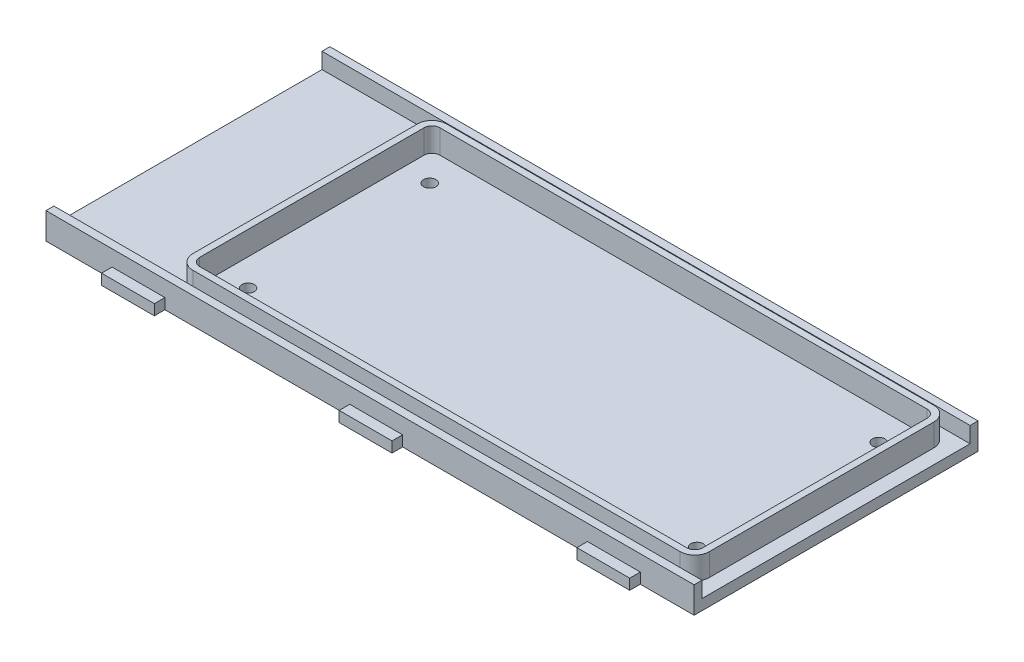
SolidWorks part; units mm, degrees
ref_plane "Front Plane" through (0, 0, 0) normal (0, 0, 1) x (1, 0, 0)
ref_plane "Top Plane" through (0, 0, 0) normal (0, 1, 0) x (1, 0, 0)
ref_plane "Right Plane" through (0, 0, 0) normal (1, 0, 0) x (0, 0, -1)
sketch "Sketch1" plane through (0, 0, 0) normal (0, 1, 0) x (1, 0, 0)
  line L0 (-61.35, 0) -> (61.35, 0) construction
  line L1 (-61.35, 26.875) -> (-48.84, 26.875)
  line L2 (-61.35, 26.875) -> (-61.35, -26.875)
  line L3 (-61.35, -26.875) -> (-48.84, -26.875)
  line L4 (61.35, 26.875) -> (61.35, -26.875)
  line L5 (-61.35, 26.875) -> (61.35, -26.875) construction
  line L6 (-61.35, -26.875) -> (61.35, 26.875) construction
  line L8 (-48.84, -26.875) -> (-48.84, -28.875)
  line L9 (-48.84, -28.875) -> (-38.84, -28.875)
  line L10 (-38.84, -26.875) -> (-38.84, -28.875)
  line L12 (-3.84, -26.875) -> (-3.84, -28.875)
  line L13 (-3.84, -28.875) -> (6.16, -28.875)
  line L14 (6.16, -26.875) -> (6.16, -28.875)
  line L16 (41.16, -26.875) -> (41.16, -28.875)
  line L17 (41.16, -28.875) -> (51.16, -28.875)
  line L18 (51.16, -26.875) -> (51.16, -28.875)
  line L19 (41.16, 28.875) -> (51.16, 28.875)
  line L20 (51.16, 26.875) -> (51.16, 28.875)
  line L22 (41.16, 26.875) -> (41.16, 28.875)
  line L23 (-3.84, 28.875) -> (6.16, 28.875)
  line L24 (6.16, 26.875) -> (6.16, 28.875)
  line L26 (-3.84, 26.875) -> (-3.84, 28.875)
  line L27 (-48.84, 28.875) -> (-38.84, 28.875)
  line L28 (-38.84, 26.875) -> (-38.84, 28.875)
  line L30 (-48.84, 26.875) -> (-48.84, 28.875)
  line L31 (-38.84, -26.875) -> (-3.84, -26.875)
  line L32 (6.16, -26.875) -> (41.16, -26.875)
  line L33 (51.16, -26.875) -> (61.35, -26.875)
  line L34 (51.16, 26.875) -> (61.35, 26.875)
  line L35 (6.16, 26.875) -> (41.16, 26.875)
  line L36 (-38.84, 26.875) -> (-3.84, 26.875)
  point P0 (0, 0)
  dimension "D1" = 53.75
  dimension "D2" = 122.7
  dimension "D3" = 10
  dimension "D4" = 10
  dimension "D5" = 10
  dimension "D6" = 2
  dimension "D7" = 2
  dimension "D8" = 2
  dimension "D9" = 12.51
  dimension "D10" = 35
  dimension "D11" = 35
extrude "Boss-Extrude1" add sketch "Sketch1" along normal blind 2
sketch "Sketch2" plane through (0, 2, 0) normal (0, 1, 0) x (1, 0, 0)
  line L0 (61.35, -26.875) -> (61.35, 26.875) construction
  line L1 (-61.35, 26.875) -> (61.35, 26.875)
  line L2 (-61.35, 26.875) -> (-61.35, 25.375)
  line L3 (-61.35, 25.375) -> (61.35, 25.375)
  line L4 (61.35, 26.875) -> (61.35, 25.375)
  line L5 (0, 0) -> (61.35, 0) construction
  line L6 (-61.35, -25.375) -> (61.35, -25.375)
  line L7 (61.35, -26.875) -> (61.35, -25.375)
  line L8 (-61.35, -26.875) -> (61.35, -26.875)
  line L9 (-61.35, -26.875) -> (-61.35, -25.375)
  dimension "D1" = 1.5
extrude "Boss-Extrude2" add sketch "Sketch2" along normal blind 3
sketch "Sketch3" plane through (0, 2, 0) normal (0, 1, 0) x (1, 0, 0)
  line L0 (-61.35, 0) -> (61.35, 0) construction
  line L1 (-36.4, 22.75) -> (55.85, 22.75)
  line L2 (-37.9, 21.25) -> (-37.9, -21.25)
  line L3 (-36.4, -22.75) -> (55.85, -22.75)
  line L4 (57.35, 21.25) -> (57.35, -21.25)
  line L5 (-37.9, 22.75) -> (57.35, -22.75) construction
  line L6 (-37.9, -22.75) -> (57.35, 22.75) construction
  line L7 (-61.35, 25.375) -> (-61.35, -25.375) construction
  line L8 (61.35, -25.375) -> (61.35, 25.375) construction
  line L9 (0, 25.375) -> (0, -25.375) construction
  line L10 (-61.35, 25.375) -> (61.35, 25.375) construction
  line L11 (61.35, -25.375) -> (-61.35, -25.375) construction
  arc A0 (55.85, 22.75) -> (57.35, 21.25) centre (55.85, 21.25) cw
  arc A1 (55.85, -22.75) -> (57.35, -21.25) centre (55.85, -21.25) ccw
  arc A2 (-36.4, -22.75) -> (-37.9, -21.25) centre (-36.4, -21.25) cw
  arc A3 (-37.9, 21.25) -> (-36.4, 22.75) centre (-36.4, 21.25) cw
  point P0 (9.725, 0)
  dimension "D4" = 1.5
  dimension "D1" = 45.5
  dimension "D2" = 95.25
  dimension "D3" = 4
extrude "Cut-Extrude1" cut sketch "Sketch3" against normal blind 0.25
sketch "Sketch4" plane through (0, 2, 0) normal (0, 1, 0) x (1, 0, 0)
  line L4 (55.85, 22.75) -> (-36.4, 22.75)
  line L5 (-37.9, 21.25) -> (-37.9, -21.25)
  line L6 (-36.4, -22.75) -> (55.85, -22.75)
  line L7 (57.35, -21.25) -> (57.35, 21.25)
  line L8 (55.85, 24) -> (-36.4, 24)
  line L9 (-39.15, 21.25) -> (-39.15, -21.25)
  line L10 (-36.4, -24) -> (55.85, -24)
  line L11 (58.6, -21.25) -> (58.6, 21.25)
  line L12 (55.85, 24) -> (-36.4, 24)
  line L13 (-39.15, 21.25) -> (-39.15, -21.25)
  line L14 (-36.4, -24) -> (55.85, -24)
  line L15 (58.6, -21.25) -> (58.6, 21.25)
  arc A4 (57.35, 21.25) -> (55.85, 22.75) centre (55.85, 21.25) ccw
  arc A5 (-36.4, 22.75) -> (-37.9, 21.25) centre (-36.4, 21.25) ccw
  arc A6 (-37.9, -21.25) -> (-36.4, -22.75) centre (-36.4, -21.25) ccw
  arc A7 (55.85, -22.75) -> (57.35, -21.25) centre (55.85, -21.25) ccw
  arc A8 (58.6, 21.25) -> (55.85, 24) centre (55.85, 21.25) ccw
  arc A9 (-36.4, 24) -> (-39.15, 21.25) centre (-36.4, 21.25) ccw
  arc A10 (-39.15, -21.25) -> (-36.4, -24) centre (-36.4, -21.25) ccw
  arc A11 (55.85, -24) -> (58.6, -21.25) centre (55.85, -21.25) ccw
  arc A12 (58.6, 21.25) -> (55.85, 24) centre (55.85, 21.25) ccw
  arc A13 (-36.4, 24) -> (-39.15, 21.25) centre (-36.4, 21.25) ccw
  arc A14 (-39.15, -21.25) -> (-36.4, -24) centre (-36.4, -21.25) ccw
  arc A15 (55.85, -24) -> (58.6, -21.25) centre (55.85, -21.25) ccw
  dimension "D1" = 1.25
  dimension "D2" = 1.25
extrude "Boss-Extrude3" add sketch "Sketch4" along normal blind 4.25
sketch "Sketch5" plane through (0, 1.75, 0) normal (0, 1, 0) x (1, 0, 0)
  line L0 (-37.9, 0) -> (57.35, 0) construction
  line L1 (-32.775, 17.2) -> (52.225, 17.2) construction
  line L2 (-32.775, 17.2) -> (-32.775, -17.2) construction
  line L3 (-32.775, -17.2) -> (52.225, -17.2) construction
  line L4 (52.225, 17.2) -> (52.225, -17.2) construction
  line L5 (-32.775, 17.2) -> (52.225, -17.2) construction
  line L6 (-32.775, -17.2) -> (52.225, 17.2) construction
  line L7 (-37.9, 21.25) -> (-37.9, -21.25) construction
  line L8 (57.35, -21.25) -> (57.35, 21.25) construction
  line L9 (9.725, 22.75) -> (9.725, -22.75) construction
  line L10 (55.85, 22.75) -> (-36.4, 22.75) construction
  line L11 (-36.4, -22.75) -> (55.85, -22.75) construction
  circle A0 centre (-32.775, 17.2) radius 1.175
  circle A1 centre (52.225, 17.2) radius 1.175
  circle A2 centre (52.225, -17.2) radius 1.175
  circle A3 centre (-32.775, -17.2) radius 1.175
  point P0 (9.725, 0)
  dimension "D3" = 2.35
  dimension "D4" = 2.35
  dimension "D5" = 2.35
  dimension "D6" = 2.35
  dimension "D1" = 85
  dimension "D2" = 34.4
extrude "Cut-Extrude2" cut sketch "Sketch5" against normal through all
